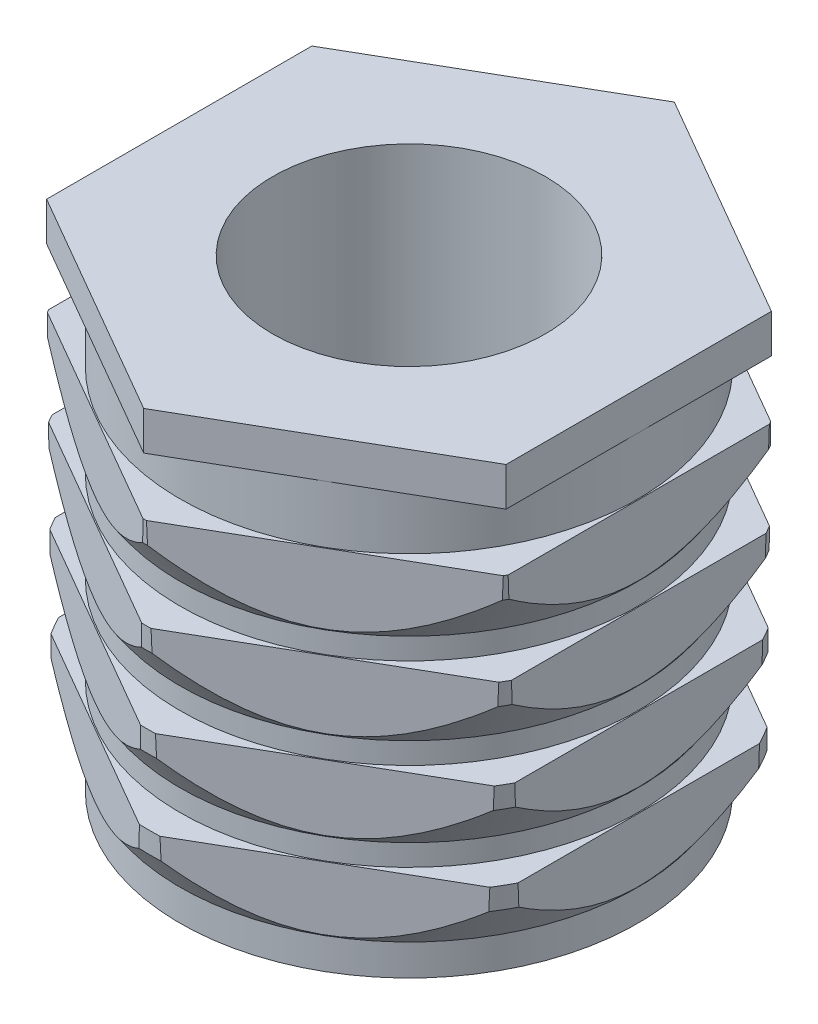
SolidWorks part; units mm, degrees
material "5052-H32"
ref_plane "Front Plane" through (0, 0, 0) normal (0, 0, 1) x (1, 0, 0)
ref_plane "Top Plane" through (0, 0, 0) normal (0, 1, 0) x (1, 0, 0)
ref_plane "Right Plane" through (0, 0, 0) normal (1, 0, 0) x (0, 0, -1)
sketch "Sketch1" plane through (0, 0, 0) normal (0, 1, 0) x (1, 0, 0)
  line L0 (-3.945, 0) -> (3.945, 0) construction
  line L1 (-3.945, 0) -> (-3.96, 0) construction
  line L2 (0, 4.5726) -> (-3.96, 2.2863)
  line L3 (-3.96, 2.2863) -> (-3.96, -2.2863)
  line L4 (-3.96, -2.2863) -> (0, -4.5726)
  line L5 (0, -4.5726) -> (3.96, -2.2863)
  line L6 (3.96, -2.2863) -> (3.96, 2.2863)
  line L7 (3.96, 2.2863) -> (0, 4.5726)
  line L8 (3.945, 0) -> (3.96, 0) construction
  line L9 (-4.5726, 0) -> (-3.96, 0) construction
  circle A0 centre (0, 0) radius 3.945 construction
  circle A1 centre (0, 0) radius 3.96 construction
  circle A2 centre (0, 0) radius 4.5726 construction
  dimension "OD" = 7.89
  dimension "Hex" = 7.92
extrude "Extrude1" add sketch "Sketch1" against normal blind 8
sketch "Sketch2" plane through (0, 0, 0) normal (0, 1, 0) x (1, 0, 0)
  circle A2 centre (0, 0) radius 3
  point P0 (-3, 0)
  dimension "Internal Thread OD" = 6
curve "Helix/Spiral1" pitch 1 height 9.5381 turns 9.5381 parameters "Internal Thread Height"=9.5381, "Internal Thread Pitch"=1
sketch "Sketch3" plane through (0, 0, 0) normal (0, 0, 1) x (1, 0, 0)
  line L0 (-2.2422, 0.5625) -> (-2.2422, -0.4375) construction
  line L1 (-2.2422, -0.4375) -> (-3.1083, 0.0625) construction
  line L2 (-3.1083, 0.0625) -> (-2.2422, 0.5625) construction
  line L3 (-2.2422, 0.0625) -> (-2.3505, 0.0625) construction
  line L4 (-2.3505, 0.0625) -> (-3, 0.0625) construction
  line L5 (-3, 0.0625) -> (-3.1083, 0.0625) construction
  line L6 (-3, 0.125) -> (-3, 0)
  line L7 (-2.3505, -0.375) -> (-2.3505, 0.5) construction
  line L11 (-3, 0) -> (-2.2964, -0.4062)
  line L12 (-2.2964, -0.4062) -> (-2.2964, 0.5312)
  line L13 (-2.2964, 0.5312) -> (-3, 0.125)
  point P18 (-2.2964, 0.0625)
  dimension "D1" = 1
  dimension "D2" = 0.125
sketch "Sketch4" plane through (0, 0, 0) normal (0, 1, 0) x (-1, 0, 0)
  circle A0 centre (0, 0) radius 2.3505
extrude "Extrude2" cut sketch "Sketch4" against normal through all
chamfer "Chamfer1" [suppressed] distance 0.75 angle 45
sketch "Sketch5" plane through (0, 0, 0) normal (0, 0, 1) x (1, 0, 0)
  line L0 (4.5726, 0) -> (-4.5726, 0) construction
  line L1 (-3.945, 0) -> (-3.945, -8) construction
  line L2 (-3.945, 0) -> (-4.5726, 0) construction
  line L3 (0, 0) -> (0, -8) construction
  line L4 (-3.96, -8) -> (0, -8) construction
  line L5 (-3.945, -8) -> (-4.5726, -8)
  line L6 (-4.5726, 0) -> (-3.96, 0) construction
  line L7 (-4.5726, 0) -> (-4.5726, -8) construction
  line L8 (-4.5726, -0.6667) -> (-4.4446, -8) construction
  line L9 (-4.5726, -0.6667) -> (-3.945, -0.6667)
  line L10 (-4.5726, 0) -> (-4.5726, -0.6667)
  line L11 (-3.945, -0.6667) -> (-3.945, -1.6667)
  line L12 (-4.4936, -5.1957) -> (-3.945, -5.9791)
  line L13 (-3.945, -8) -> (-3.945, -7.4624)
  line L14 (-3.945, -5.9791) -> (-3.945, -6.348)
  line L15 (-3.945, -1.6667) -> (-4.5552, -1.6667)
  line L16 (-4.5552, -1.6667) -> (-4.5487, -2.0355)
  line L17 (-4.5487, -2.0355) -> (-3.945, -2.8977)
  line L18 (-3.945, -6.348) -> (-4.4734, -6.348)
  line L19 (-4.5726, 0) -> (-5.2002, 0)
  line L20 (-5.2002, 0) -> (-5.2002, -8)
  line L21 (-5.2002, -8) -> (-4.5726, -8)
  line L22 (-3.945, -3.2667) -> (-4.5272, -3.2667)
  line L23 (-3.945, -2.8977) -> (-3.945, -3.2667)
  line L24 (-4.5272, -3.2667) -> (-4.5208, -3.6355)
  line L25 (-4.5208, -3.6355) -> (-3.945, -4.4579)
  line L26 (-3.945, -4.8268) -> (-4.5, -4.8268)
  line L27 (-4.5, -4.8268) -> (-4.4936, -5.1957)
  line L28 (-4.4734, -6.348) -> (-4.467, -6.7169)
  line L29 (-3.945, -4.4579) -> (-3.945, -4.8268)
  line L30 (-4.467, -6.7169) -> (-3.945, -7.4624)
  dimension "D1" = 0.6667
  dimension "D2" = 1
  dimension "D5" = 35
  dimension "D6" = 1
  dimension "D3" = 1.6
revolve "Cut-Revolve1" cut sketch "Sketch5" angle 360 about L3
sketch "Sketch6" [suppressed] plane through (0, 0, 0) normal (0, 1, 0) x (1, 0, 0)
  line L0 (0, 0) -> (2.1924, -2.1924) construction
  line L1 (0, 0) -> (0, -4.5726) construction
  circle A0 centre (0, 0) radius 3.1005 construction
  point P8 (2.1924, -2.1924)
  dimension "D1" = 45
ref_plane "Contact Plane 1" through (0, 0, 0) normal (0, 1, 0) x (1, 0, 0)
ref_plane "Contact Plane 2" through (0, -8, 0) normal (0, -1, 0) x (-1, 0, 0)
ref_axis "Center Axis 1" [suppressed] through (0, -7.25, 0) along (0, 1, 0)
sweep "Cut-Sweep1" [suppressed] cut profiles "Sketch3" path "Helix/Spiral1"
equation "\"Internal Thread Height@Helix/Spiral1\" = \"Internal Thread Pitch@Helix/Spiral1\" + \"Length@Extrude1\" + 0.5381"
equation "\"D1@Sketch3\" = \"Internal Thread Pitch@Helix/Spiral1\""
equation "\"D2@Sketch3\" = \"D1@Sketch3\" * 1 / 8"
equation "\"D1@Chamfer1\" = \"Internal Thread Pitch@Helix/Spiral1\" * 6 / 8"
equation "\"D1@Sketch5\" = \"Length@Extrude1\"  * 1 / 12"
equation "\"D6@Sketch5\" = \"D1@Sketch5\" * 1.5"
equation "\"D3@Sketch5\" = \"Length@Extrude1\"  * 1 / 5"
